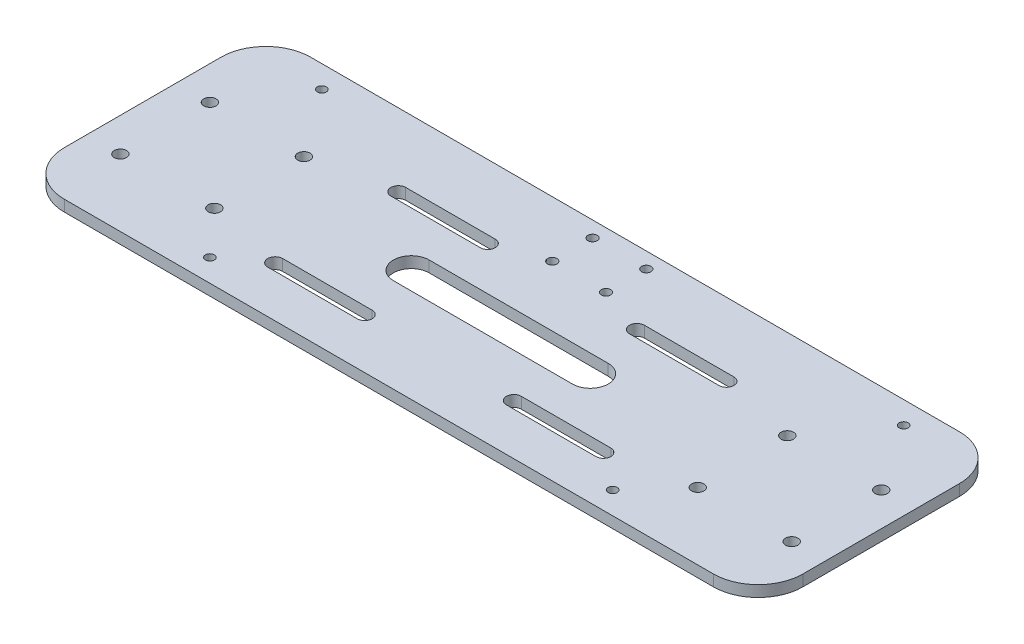
SolidWorks part; units mm, degrees
ref_plane "前视基准面" through (0, 0, 0) normal (0, 0, 1) x (1, 0, 0)
ref_plane "上视基准面" through (0, 0, 0) normal (0, 1, 0) x (1, 0, 0)
ref_plane "右视基准面" through (0, 0, 0) normal (1, 0, 0) x (0, 0, -1)
sketch "草图1" plane through (0, 0, 0) normal (0, 1, 0) x (1, 0, 0)
  line L1 (-155.3696, -90.2724) -> (174.6304, -90.2724)
  line L2 (-155.3696, -90.2724) -> (-155.3696, -200.2724)
  line L3 (-155.3696, -200.2724) -> (174.6304, -200.2724)
  line L4 (174.6304, -90.2724) -> (174.6304, -200.2724)
  dimension "D1" = 330
  dimension "D2" = 110
extrude "凸台-拉伸1" add sketch "草图1" along normal blind 5
sketch "草图3" plane through (0, 5, 0) normal (0, 1, 0) x (1, 0, 0)
  line L0 (9.6304, -73.8743) -> (9.6304, -261.3849) construction
  line L1 (-2.3696, -97.2724) -> (-2.3696, -133.7579) construction
  line L2 (174.6304, -90.2724) -> (-155.3696, -90.2724) construction
  circle A0 centre (-2.3696, -97.2724) radius 2.1
  circle A1 centre (21.6304, -97.2724) radius 2.1
  circle A2 centre (-2.3696, -115.2724) radius 2.1
  circle A3 centre (21.6304, -115.2724) radius 2.1
  point P13 (9.6304, -90.2724)
  dimension "D1" = 4.2
  dimension "D7" = 4.2
  dimension "D8" = 4.2
  dimension "D2" = 24
  dimension "D3" = 18
  dimension "D4" = 18
  dimension "D5" = 24
  dimension "D6" = 7
extrude "切除-拉伸1" cut sketch "草图3" against normal through all
sketch "草图4" plane through (0, 5, 0) normal (0, 1, 0) x (1, 0, 0)
  line L0 (-155.3696, -150.2724) -> (174.6304, -150.2724) construction
  line L1 (-155.3696, -90.2724) -> (-155.3696, -200.2724) construction
  line L2 (174.6304, -200.2724) -> (174.6304, -90.2724) construction
  line L3 (9.6304, -149.3208) -> (9.6304, -90.2724) construction
  line L4 (-30.3696, -150.2724) -> (49.6304, -150.2724) construction
  line L5 (-63.6837, -122.7724) -> (-23.6837, -122.7724) construction
  line L6 (-30.3696, -142.2724) -> (49.6304, -142.2724)
  line L7 (-30.3696, -158.2724) -> (49.6304, -158.2724)
  line L8 (174.6304, -90.2724) -> (-155.3696, -90.2724) construction
  line L9 (-63.6837, -119.4432) -> (-23.6837, -119.4432)
  line L10 (-63.6837, -126.1015) -> (-23.6837, -126.1015)
  line L11 (82.9444, -122.7724) -> (42.9444, -122.7724) construction
  line L12 (82.9444, -119.4432) -> (42.9444, -119.4432)
  line L13 (82.9444, -126.1015) -> (42.9444, -126.1015)
  line L14 (-63.6837, -177.7724) -> (-23.6837, -177.7724) construction
  line L15 (-63.6837, -181.1015) -> (-23.6837, -181.1015)
  line L16 (-63.6837, -174.4432) -> (-23.6837, -174.4432)
  line L17 (82.9444, -177.7724) -> (42.9444, -177.7724) construction
  line L18 (82.9444, -181.1015) -> (42.9444, -181.1015)
  line L19 (82.9444, -174.4432) -> (42.9444, -174.4432)
  circle A0 centre (-140.3696, -170.2724) radius 2.75
  circle A1 centre (-140.3696, -130.2724) radius 2.75
  circle A2 centre (-98.3696, -170.2724) radius 2.75
  circle A3 centre (-98.3696, -130.2724) radius 2.75
  circle A4 centre (117.6304, -130.2724) radius 2.75
  circle A5 centre (117.6304, -170.2724) radius 2.75
  circle A6 centre (159.6304, -130.2724) radius 2.75
  circle A7 centre (159.6304, -170.2724) radius 2.75
  arc A8 (-30.3696, -142.2724) -> (-30.3696, -158.2724) centre (-30.3696, -150.2724) ccw
  arc A9 (49.6304, -158.2724) -> (49.6304, -142.2724) centre (49.6304, -150.2724) ccw
  arc A10 (-63.6837, -119.4432) -> (-63.6837, -126.1015) centre (-63.6837, -122.7724) ccw
  arc A11 (-23.6837, -126.1015) -> (-23.6837, -119.4432) centre (-23.6837, -122.7724) ccw
  arc A12 (82.9444, -119.4432) -> (82.9444, -126.1015) centre (82.9444, -122.7724) cw
  arc A13 (42.9444, -126.1015) -> (42.9444, -119.4432) centre (42.9444, -122.7724) cw
  arc A14 (-63.6837, -181.1015) -> (-63.6837, -174.4432) centre (-63.6837, -177.7724) cw
  arc A15 (-23.6837, -174.4432) -> (-23.6837, -181.1015) centre (-23.6837, -177.7724) cw
  arc A16 (82.9444, -181.1015) -> (82.9444, -174.4432) centre (82.9444, -177.7724) ccw
  arc A17 (42.9444, -174.4432) -> (42.9444, -181.1015) centre (42.9444, -177.7724) ccw
  point P28 (9.6304, -150.2724)
  point P36 (-43.6837, -122.7724)
  point P44 (62.9444, -122.7724)
  point P51 (-43.6837, -177.7724)
  point P58 (62.9444, -177.7724)
  dimension "D1" = 5.5
  dimension "D3" = 42
  dimension "D8" = 8
  dimension "D9" = 5.5
  dimension "D10" = 60
  dimension "D5" = 55
  dimension "D2" = 20
  dimension "D4" = 15
  dimension "D6" = 80
extrude "切除-拉伸2" cut sketch "草图4" against normal through all
sketch "草图5" plane through (0, 5, 0) normal (0, 1, 0) x (1, 0, 0)
  line L0 (9.6304, -90.2724) -> (9.6304, 49909.7276) construction
  line L1 (174.6304, -90.2724) -> (-155.3696, -90.2724) construction
  line L2 (-155.3696, -200.2724) -> (174.6304, -200.2724) construction
  circle A0 centre (-120.3696, -100.2724) radius 2
  circle A1 centre (139.6304, -100.2724) radius 2
  circle A2 centre (-80.3696, -190.2724) radius 2
  circle A3 centre (99.6304, -190.2724) radius 2
  point P4 (9.6304, -90.2724)
  dimension "D1" = 4
  dimension "D3" = 10
  dimension "D4" = 10
  dimension "D5" = 90
  dimension "D2" = 130
  dimension "D6" = 90
  dimension "D7" = 10
extrude "切除-拉伸3" cut sketch "草图5" against normal through all
fillet "圆角1" radius 20 4 edges at (174.6304, 2.5, 200.2724) (174.6304, 2.5, 90.2724) (-155.3696, 2.5, 90.2724) (-155.3696, 2.5, 200.2724)
